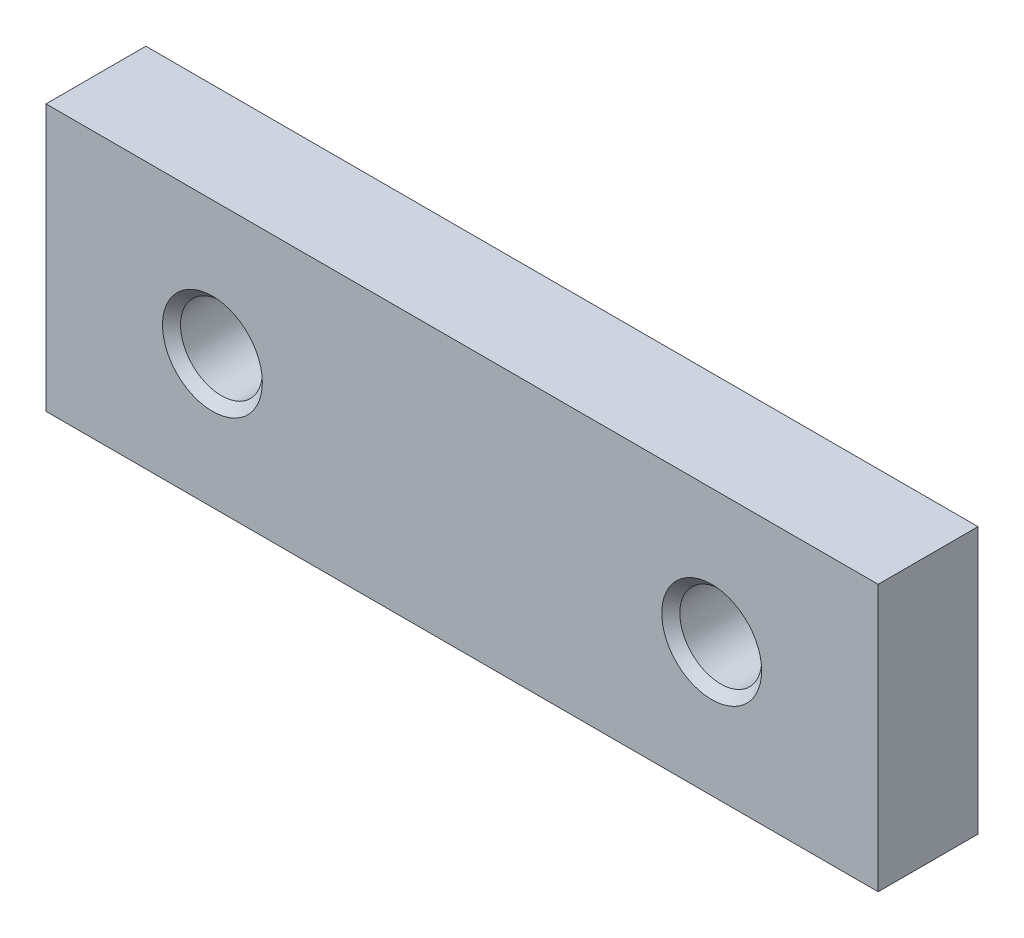
SolidWorks part; units mm, degrees
ref_plane "Front" through (0, 0, 0) normal (0, 0, 1) x (1, 0, 0)
ref_plane "Top" through (0, 0, 0) normal (0, 1, 0) x (1, 0, 0)
ref_plane "Right" through (0, 0, 0) normal (1, 0, 0) x (0, 0, -1)
ref_plane "Plane1" through (0, 0, 0) normal (0, 0, 1) x (1, 0, 0)
sketch "Sketch1" plane through (0, 0, 0) normal (0, 0, 1) x (1, 0, 0)
  line L0 (-10, -8) -> (40, -8)
  line L1 (40, -8) -> (40, 8)
  line L2 (40, 8) -> (-10, 8)
  line L3 (-10, 8) -> (-10, -8)
extrude "Boss-Extrude1" add sketch "Sketch1" against normal blind 3 and the other way blind 3
ref_plane "Plane2" through (0, 0, 0) normal (1, 0, 0) x (0, 0, -1)
sketch "Sketch2" plane through (0, 0, 0) normal (1, 0, 0) x (0, 0, -1)
  line L0 (-3, 0) -> (-3, 3)
  line L1 (-3, 3) -> (-2.4585, 2.4585)
  line L2 (-2.4585, 2.4585) -> (2.4585, 2.4585)
  line L3 (2.4585, 2.4585) -> (3, 3)
  line L4 (3, 3) -> (3, 0)
  line L5 (3, 0) -> (-3, 0)
  line L6 (3, 0) -> (-3, 0) construction
revolve "Cut-Revolve1" cut sketch "Sketch2" angle 360 about L6 reverse direction yes
cosmetic thread "Cosmetic Thread1"
ref_plane "Plane3" through (30, 0, 0) normal (1, 0, 0) x (0, 0, -1)
sketch "Sketch3" plane through (30, 0, 0) normal (1, 0, 0) x (0, 0, -1)
  line L0 (-3, 0) -> (-3, 3)
  line L1 (-3, 3) -> (-2.4585, 2.4585)
  line L2 (-2.4585, 2.4585) -> (2.4585, 2.4585)
  line L3 (2.4585, 2.4585) -> (3, 3)
  line L4 (3, 3) -> (3, 0)
  line L5 (3, 0) -> (-3, 0)
  line L6 (3, 0) -> (-3, 0) construction
revolve "Cut-Revolve2" cut sketch "Sketch3" angle 360 about L6 reverse direction yes
cosmetic thread "Cosmetic Thread2" parameters "D1"=6, "D2"=6
